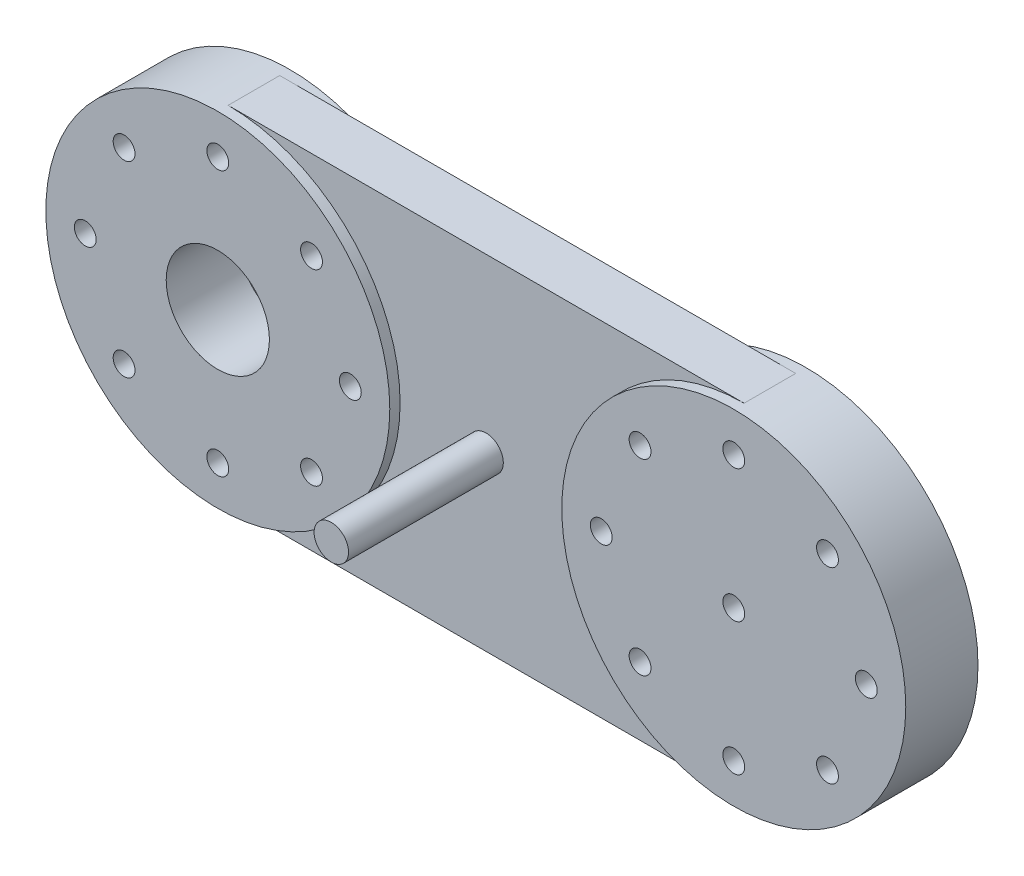
SolidWorks part; units mm, degrees
note: The reader was unsure of these and kept them because the rebuilt part matched: shared geometry of "草图1<17>", "草图1<30>", "草图1<31>", "草图1<33>".
ref_plane "前视基准面" through (0, 0, 0) normal (0, 0, 1) x (1, 0, 0)
ref_plane "上视基准面" through (0, 0, 0) normal (0, 1, 0) x (1, 0, 0)
ref_plane "右视基准面" through (0, 0, 0) normal (1, 0, 0) x (0, 0, -1)
sketch "草图1" plane through (0, 0, 0) normal (0, 0, 1) x (1, 0, 0)
  line L0 (0, 50) -> (-150, 50)
  line L5 (0, 0) -> (-150, 0)
  line L6 (0, 0) -> (0, 100)
  line L7 (0, 100) -> (-150, 100)
  line L8 (-150, 0) -> (-150, 100)
  line L10 (-114.6447, 85.3553) -> (-185.3553, 14.6447)
  line L12 (-114.6447, 85.3553) -> (-185.3553, 85.3553)
  line L13 (-114.6447, 85.3553) -> (-114.6447, 14.6447)
  line L14 (-114.6447, 14.6447) -> (-185.3553, 14.6447)
  line L15 (-185.3553, 85.3553) -> (-185.3553, 14.6447)
  circle A6 centre (0, 50) radius 50
  circle A7 centre (0, 50) radius 25
  circle A8 centre (-150, 50) radius 50
  circle A9 centre (-150, 50) radius 25
  circle A10 centre (-75, 50) radius 5
  circle A11 centre (-111.4697, 50) radius 3.175
  circle A12 centre (-122.7549, 22.7549) radius 3.175
  circle A13 centre (-150, 11.4697) radius 3.175
  circle A14 centre (-177.2451, 22.7549) radius 3.175
  circle A15 centre (-188.5303, 50) radius 3.175
  circle A16 centre (-177.2451, 77.2451) radius 3.175
  circle A17 centre (-150, 88.5303) radius 3.175
  circle A18 centre (-122.7549, 77.2451) radius 3.175
  circle A19 centre (38.5303, 50) radius 3.175
  circle A20 centre (27.2451, 22.7549) radius 3.175
  circle A21 centre (0, 11.4697) radius 3.175
  circle A22 centre (-27.2451, 22.7549) radius 3.175
  circle A23 centre (-38.5303, 50) radius 3.175
  circle A24 centre (-27.2451, 77.2451) radius 3.175
  circle A25 centre (0, 88.5303) radius 3.175
  circle A26 centre (27.2451, 77.2451) radius 3.175
  circle A27 centre (-150, 50) radius 3.175
  circle A28 centre (0, 50) radius 3.175
  point P35 (-150, 50)
  point P39 (-75, 50)
  point P54 (0, 50)
  dimension "D1" = 100
  dimension "D2" = 150
  dimension "D3" = 50
  dimension "D4" = 50
  dimension "D5" = 10
  dimension "D6" = 6.35
  dimension "D10" = 6.35
  dimension "D11" = 6.35
  dimension "D7" = 8
  dimension "D8" = 2
  dimension "D9" = 8
extrude "short_arm_body" add sketch "草图1" against normal blind 15 contours L7 L8 L5 L6
extrude "凸台-拉伸8" add sketch "草图1<17>" along normal blind 45 contours A10
sketch "草图1<17>" plane through (0, 0, 0) normal (0, 0, 1) x (1, 0, 0) same geometry as "草图1"
extrude "凸台-拉伸10" add sketch "草图1<30>" along normal blind 3 contours A23 L0 A6 L6 A21 A7 A22 | L0 A7 L6 | L6 A7 L0 | A25 L6 A6 L0 A23 A7 A24
sketch "草图1<30>" plane through (0, 0, 0) normal (0, 0, 1) x (1, 0, 0) same geometry as "草图1"
extrude "切除-拉伸1" cut sketch "草图1<31>" along normal blind 88 and the other way blind 59 contours A8 | A6
sketch "草图1<31>" plane through (0, 0, 0) normal (0, 0, 1) x (1, 0, 0) same geometry as "草图1"
extrude "凸台-拉伸12" add sketch "草图1<33>" against normal blind 18 and the other way blind 3 contours A11 L0 A8 L13 | A18 L10 A9 L0 L13 | A18 L10 L12 L8 A9 | A17 L12 A8 L8 | A17 L8 A8 L12 | A14 L10 A9 L8 L12 L15 A16 | L15 A15 A8 | A14 L10 L14 L8 A9 | A13 L14 A8 L8 | A9 L8 L14 L13 L0 A12 | A13 L8 A8 L14 | A27 L8 A9 L0 | A27 L8 A9 L10 | A27 L10 A9 L8 | A27 L0 A9 L10 | A27 L10 A9 L8 | A11 L13 A8 L0 | A23 L0 A6 L6 A21 A7 A22 | A25 L6 A6 L0 A23 A7 A24 | A25 L6 A7 A21 A6 A26 A20 A19 | A28 L6 A7 | A28 L6 A7 L0 | A28 L0 A7 L6
sketch "草图1<33>" plane through (0, 0, 0) normal (0, 0, 1) x (1, 0, 0) same geometry as "草图1"
sketch "草图3" plane through (0, 0, -18) normal (0, 0, -1) x (-1, 0, 0)
  circle A0 centre (150, 50) radius 15
  dimension "D1" = 30
extrude "切除-拉伸3" cut sketch "草图3" against normal blind 98 contours A0
